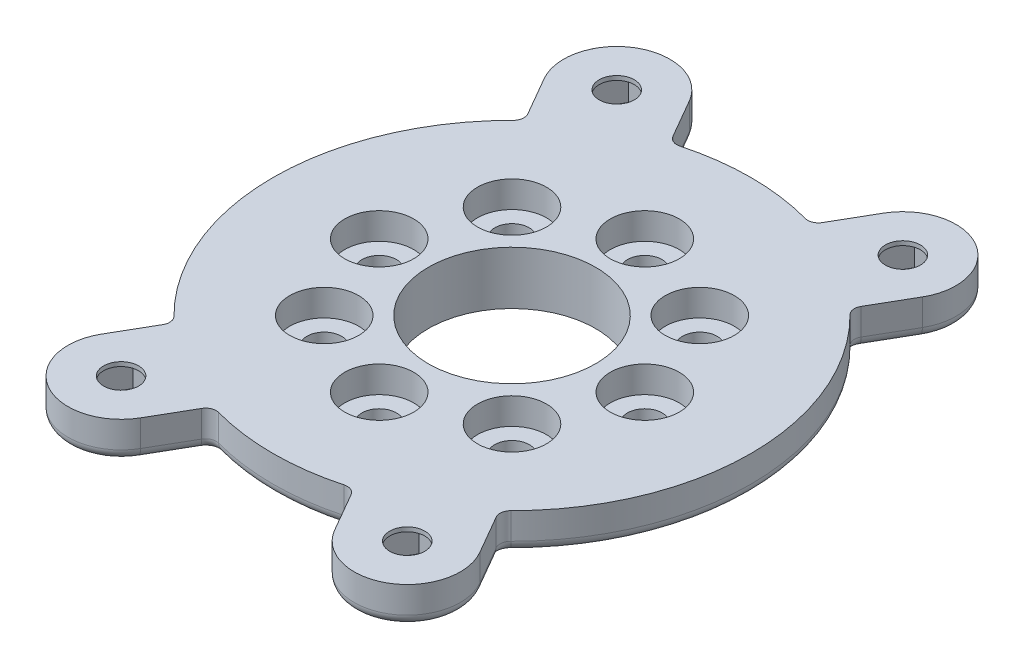
SolidWorks part; units mm, degrees
ref_plane "Front Plane" through (0, 0, 0) normal (0, 0, 1) x (1, 0, 0)
ref_plane "Top Plane" through (0, 0, 0) normal (0, 1, 0) x (1, 0, 0)
ref_plane "Right Plane" through (0, 0, 0) normal (1, 0, 0) x (0, 0, -1)
sketch "Sketch1" plane through (0, 0, 0) normal (0, 1, 0) x (1, 0, 0)
  circle A0 centre (0, 0) radius 45
  dimension "D1" = 90
extrude "Boss-Extrude1" add sketch "Sketch1" along normal blind 7
sketch "Sketch10" plane through (0, 0, 0) normal (0, 1, 0) x (1, 0, 0)
  circle A0 centre (0, 0) radius 31.5
  dimension "D1" = 63
extrude "Boss-Extrude3" add sketch "Sketch10" against normal blind 3
sketch "Sketch12" plane through (0, 0, 0) normal (0, 1, 0) x (1, 0, 0)
  circle A0 centre (0, 0) radius 15.75
  dimension "D1" = 31.5
extrude "Cut-Extrude1" cut sketch "Sketch12" against normal through all both and the other way through all
hole_wizard "CBORE for M6 Hex Head Bolt4" positions "Sketch17" profile "Sketch18" counterbore size "M6" standard "DIN" end condition through all
sketch "Sketch17" plane through (0, 7, 0) normal (0, 1, 0) x (1, 0, 0)
  point P0 (0, 25)
  dimension "D1" = 25
sketch "Sketch18" plane through (0, 7, -25) normal (1, 0, 0) x (0, 0, 1)
  line L0 (0, 0) -> (0, 10)
  line L1 (0, 10) -> (3.25, 10)
  line L3 (3.25, 10) -> (3.25, 5)
  line L4 (3.25, 5) -> (6.5, 5)
  line L5 (6.5, 5) -> (6.5, 0)
  line L7 (6.5, 0) -> (0, 0)
  line L11 (0, -6.35) -> (0, 107.95) construction
  dimension "Thru Hole Dia." = 6.5
  dimension "Thru Hole Depth" = 10
  dimension "C'Bore Dia." = 13
  dimension "C'Bore Depth" = 5
pattern_circular "CirPattern11" count 8 over 360 about axis through (0, 7, 0) along (0, -1, 0) of "CBORE for M6 Hex Head Bolt4"
sketch "Sketch19" plane through (0, 7, 0) normal (0, 1, 0) x (1, 0, 0)
  line L0 (0, 0) -> (0, 45) construction
  line L1 (0, 0) -> (-22.5, 38.9711) construction
  line L3 (-30.5977, 32.9967) -> (-35.5977, 41.657)
  line L4 (-13.2772, 42.9967) -> (-18.2772, 51.657)
  line L6 (0, -3.85) -> (0, 3.85) construction
  line L7 (13.2772, 42.9967) -> (18.2772, 51.657)
  line L8 (30.5977, 32.9967) -> (35.5977, 41.657)
  line L9 (-3.85, 0) -> (3.85, 0) construction
  line L10 (30.5977, -32.9967) -> (35.5977, -41.657)
  line L11 (13.2772, -42.9967) -> (18.2772, -51.657)
  line L12 (-13.2772, -42.9967) -> (-18.2772, -51.657)
  line L13 (-30.5977, -32.9967) -> (-35.5977, -41.657)
  line L14 (-30.5977, 32.9967) -> (-13.2772, 42.9967)
  line L15 (13.2772, 42.9967) -> (30.5977, 32.9967)
  line L16 (-30.5977, -32.9967) -> (-13.2772, -42.9967)
  line L17 (13.2772, -42.9967) -> (30.5977, -32.9967)
  circle A0 centre (0, 0) radius 45 construction
  arc A1 (-35.5977, 41.657) -> (-18.2772, 51.657) centre (-26.9374, 46.657) cw
  arc A2 (35.5977, 41.657) -> (18.2772, 51.657) centre (26.9374, 46.657) ccw
  arc A3 (35.5977, -41.657) -> (18.2772, -51.657) centre (26.9374, -46.657) cw
  arc A4 (-35.5977, -41.657) -> (-18.2772, -51.657) centre (-26.9374, -46.657) ccw
  dimension "D1" = 30
  dimension "D2" = 10
  dimension "D3" = 20
extrude "Boss-Extrude4" add sketch "Sketch19" against normal blind 7
hole_wizard "M6 Clearance Hole1" positions "Sketch20" profile "Sketch21" hole size "M6" standard "DIN" end condition through all
sketch "Sketch20" plane through (0, 7, 0) normal (0, 1, 0) x (1, 0, 0)
  point P0 (-26.9374, 46.657)
  point P3 (26.9374, 46.657)
  point P6 (-26.9374, -46.657)
  point P9 (26.9374, -46.657)
sketch "Sketch21" plane through (-26.9374, 7, -46.657) normal (1, 0, 0) x (0, 0, 1)
  line L0 (0, 0) -> (0, 10)
  line L1 (0, 10) -> (3.3, 10)
  line L2 (3.3, 10) -> (3.3, 0)
  line L5 (3.3, 0) -> (0, 0)
  line L11 (0, -6.35) -> (0, 107.95) construction
  dimension "Thru Hole Dia." = 6.6
  dimension "Thru Hole Depth" = 10
fillet "Fillet5" radius 2 24 edges at (-31.9374, 0, 55.3172) (-33.0977, 0, 37.3268) (-15.7772, 0, 47.3268) (-45, 0, 0) (0, 0, 45) (-33.0977, 0, -37.3268) (-31.9374, 0, -55.3172) (15.7772, 0, -47.3268) (31.9374, 0, -55.3172) (15.7772, 0, 47.3268) (30.5977, 3.5, 32.9967) (13.2772, 3.5, 42.9967) (-13.2772, 3.5, 42.9967) (-30.5977, 3.5, 32.9967) (-30.5977, 3.5, -32.9967) (-13.2772, 3.5, -42.9967) (30.5977, 3.5, -32.9967) (13.2772, 3.5, -42.9967) (0, 0, -45) (-15.7772, 0, -47.3268) (33.0977, 0, -37.3268) (31.9374, 0, 55.3172) (33.0977, 0, 37.3268) (45, 0, 0)
ref_plane "Plane1" through (0, 3.5, 0) normal (0, 1, 0) x (1, 0, 0)
sketch "Sketch22" plane through (0, 3.5, 0) normal (0, 1, 0) x (1, 0, 0)
  line L0 (-31.3814, -34.3542) -> (-35.5977, -41.657) construction
  line L1 (-23.9063, -41.407) -> (-29.9685, -41.407)
  line L2 (-29.9685, -41.407) -> (-32.9996, -46.657)
  line L3 (-32.9996, -46.657) -> (-29.9685, -51.907)
  line L4 (-29.9685, -51.907) -> (-23.9063, -51.907)
  line L5 (-23.9063, -51.907) -> (-20.8752, -46.657)
  line L6 (-20.8752, -46.657) -> (-23.9063, -41.407)
  circle A0 centre (-26.9374, -46.657) radius 5.25 construction
  point P11 (-22.3908, -49.282)
  dimension "D1" = 10.5
extrude "Cut-Extrude2" cut sketch "Sketch22" against normal blind 2.7 and the other way blind 2.7
mirror "Mirror1" about plane through (0, 0, 0) normal (1, 0, 0) of "Cut-Extrude2"
mirror "Mirror2" about plane through (0, 0, 0) normal (0, 0, 1) of "Mirror1", "Cut-Extrude2"
fillet "Fillet7" radius 3 1 edges at (0, 0, 31.5)
